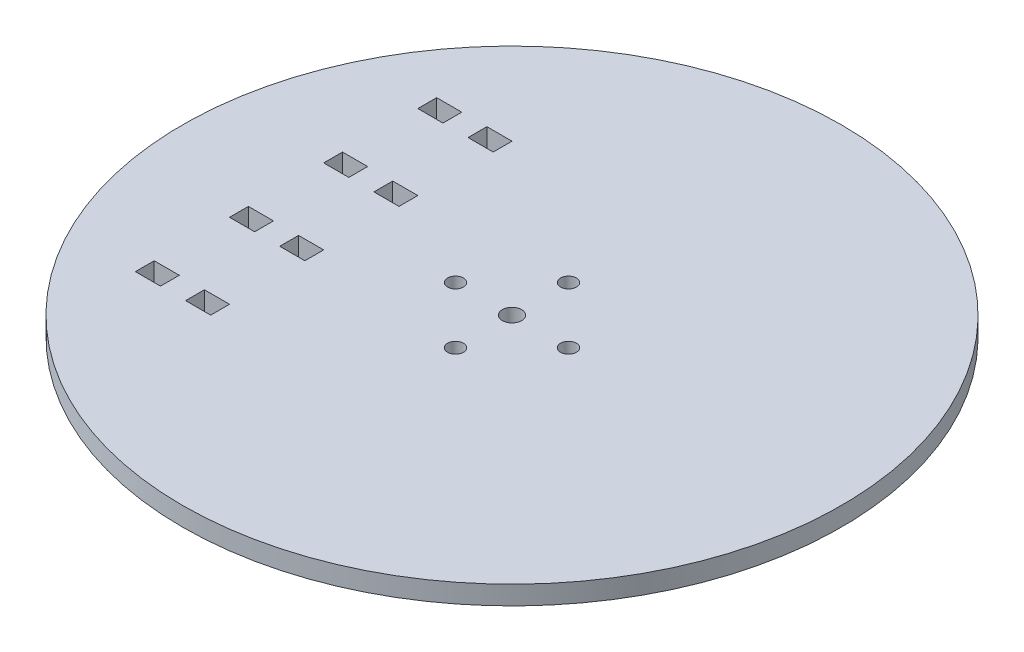
SolidWorks part; units mm, degrees
ref_plane "Front Plane" through (0, 0, 0) normal (0, 0, 1) x (1, 0, 0)
ref_plane "Top Plane" through (0, 0, 0) normal (0, 1, 0) x (1, 0, 0)
ref_plane "Right Plane" through (0, 0, 0) normal (1, 0, 0) x (0, 0, -1)
sketch "Sketch1" plane through (0, 0, 0) normal (0, 1, 0) x (1, 0, 0)
  circle A0 centre (0, 0) radius 87.5
  dimension "D1" = 175
extrude "Boss-Extrude1" add sketch "Sketch1" along normal blind 5
sketch "Sketch2" plane through (0, 5, 0) normal (0, 1, 0) x (1, 0, 0)
  line L1 (-1018.973, 15) -> (48981.027, 15) construction
  line L2 (-1018.8066, 10) -> (48981.1934, 10) construction
  line L5 (-60, 15) -> (-53.3333, 15)
  line L6 (-60, 15) -> (-60, 10)
  line L7 (-60, 10) -> (-53.3333, 10)
  line L8 (-53.3333, 15) -> (-53.3333, 10)
  line L9 (-46.6667, 15) -> (-40, 15)
  line L10 (-46.6667, 15) -> (-46.6667, 10)
  line L11 (-46.6667, 10) -> (-40, 10)
  line L12 (-40, 15) -> (-40, 10)
  dimension "D3" = 5
  dimension "D1" = 10
  dimension "D5" = 6.6667
  dimension "D6" = 6.6667
  dimension "D7" = 20
  dimension "D8" = 60
extrude "Cut-Extrude1" cut sketch "Sketch2" against normal through all
mirror "Mirror1" about plane through (0, 0, 0) normal (0, 0, 1) of "Cut-Extrude1"
pattern_linear "LPattern1" count 2 spacing 25 along (0, 0, -1) of "Cut-Extrude1"
pattern_linear "LPattern2" count 2 spacing 25 along (0, 0, 1) of "Mirror1"
sketch "Sketch3" plane through (0, 5, 0) normal (0, 1, 0) x (1, 0, 0)
  line L0 (0, -1000) -> (0, 49000) construction
  circle A0 centre (0, 15) radius 2.1
  dimension "D1" = 4.2
  dimension "D2" = 15
extrude "Cut-Extrude2" cut sketch "Sketch3" against normal through all
pattern_circular "CirPattern1" count 4 over 360 about axis through (0, 5, 0) along (0, -1, 0) of "Cut-Extrude2"
sketch "Sketch4" plane through (0, 5, 0) normal (0, 1, 0) x (1, 0, 0)
  circle A0 centre (0, 0) radius 2.55
  dimension "D1" = 5.1
extrude "Cut-Extrude3" cut sketch "Sketch4" against normal blind 10
